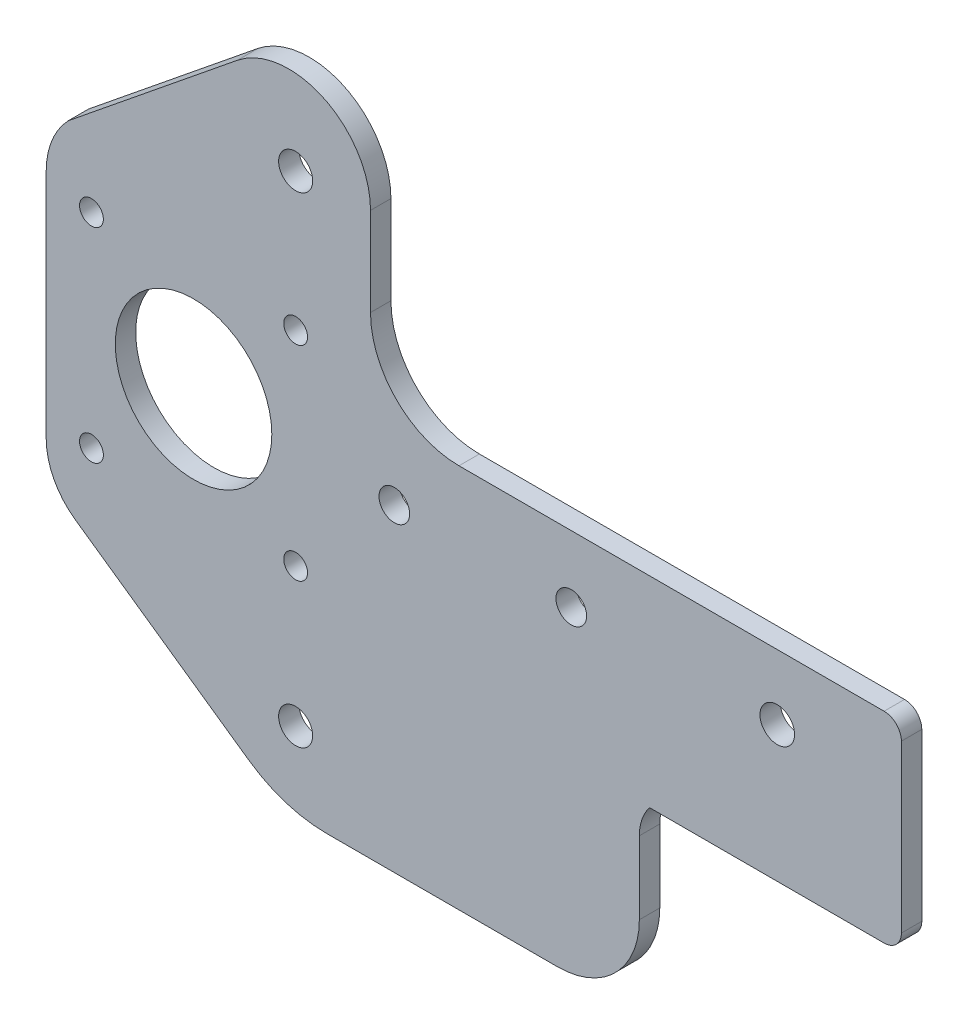
SolidWorks part; units mm, degrees
ref_plane "Front Plane" through (0, 0, 0) normal (0, 0, 1) x (1, 0, 0)
ref_plane "Top Plane" through (0, 0, 0) normal (0, 1, 0) x (1, 0, 0)
ref_plane "Right Plane" through (0, 0, 0) normal (1, 0, 0) x (0, 0, -1)
sketch "Sketch1" plane through (0, 0, 0) normal (0, 0, 1) x (1, 0, 0)
  line L0 (0, 0) -> (0, -29.5)
  line L1 (0, -29.5) -> (-37, -29.5)
  line L2 (0, 0) -> (-65, 0)
  line L3 (-78, 13) -> (-78, 26)
  line L4 (-97.5518, 35.3258) -> (-122.4205, 15.1875)
  line L5 (-125.65, 7.1517) -> (-125.65, -26.8483)
  line L6 (-89, 5.25) -> (-89, -24.75) construction
  line L7 (-119, 5.25) -> (-89, 5.25) construction
  line L8 (-121.3858, -35.0398) -> (-95.8858, -52.8951)
  line L9 (-84.4142, -56.5121) -> (-50.5, -56.5121)
  line L10 (-38.5, -44.5121) -> (-38.5, -33.8301)
  line L11 (-104, -9.75) -> (-104, 5.25) construction
  line L12 (-104, -9.75) -> (-89, -9.75) construction
  arc A0 (-78, 13) -> (-65, 0) centre (-65, 13) ccw
  arc A1 (-78, 26) -> (-97.5518, 35.3258) centre (-90, 26) ccw
  arc A2 (-122.4205, 15.1875) -> (-125.65, 7.1517) centre (-114.0376, 7.1517) ccw
  arc A3 (-125.65, -26.8483) -> (-121.3858, -35.0398) centre (-115.65, -26.8483) ccw
  arc A4 (-95.8858, -52.8951) -> (-84.4142, -56.5121) centre (-84.4142, -36.5121) ccw
  arc A5 (-50.5, -56.5121) -> (-38.5, -44.5121) centre (-50.5, -44.5121) ccw
  arc A6 (-37, -29.5) -> (-38.5, -33.8301) centre (-31.5, -33.8301) ccw
  circle A7 centre (-18.237, -9.552) radius 2.54
  circle A8 centre (-48.5, -9.75) radius 2.25
  circle A9 centre (-74.5, -9.75) radius 2.25
  circle A10 centre (-89, 5.25) radius 1.75
  circle A11 centre (-89, 25.5) radius 2.5
  circle A12 centre (-89, -24.75) radius 1.75
  circle A13 centre (-89, -45.112) radius 2.5
  circle A14 centre (-104, -9.75) radius 11.5
  circle A15 centre (-119, 5.25) radius 1.75
  circle A16 centre (-119, -24.75) radius 1.75
  dimension "D4" = 24
  dimension "D5" = 26
  dimension "D9" = 56.263
  dimension "D12" = 20
  dimension "D13" = 26
  dimension "D16" = 14
  dimension "D17" = 24
  dimension "D19" = 5.08
  dimension "D20" = 4.5
  dimension "D21" = 4.5
  dimension "D22" = 30
  dimension "D23" = 5
  dimension "D24" = 61.7621
  dimension "D25" = 5
  dimension "D26" = 30
  dimension "D27" = 23
  dimension "D11" = 3.5
  dimension "D1" = 65
  dimension "D2" = 29.5
  dimension "D3" = 37
  dimension "D6" = 13
  dimension "D7" = 32
  dimension "D8" = 51
  dimension "D10" = 34
  dimension "D14" = 125
  dimension "D15" = 25.5
  dimension "D18" = 1.5
  dimension "D29" = 70.763
  dimension "D30" = 9.75
  dimension "D31" = 9.75
  dimension "D34" = 25.5
  dimension "D37" = 70.612
  dimension "D39" = 35.56
  dimension "D42" = 89
extrude "Boss-Extrude1" add sketch "Sketch1" along normal blind 3
fillet "Fillet2" radius 2.54 2 edges at (0, 0, 1.5) (0, -29.5, 1.5)
